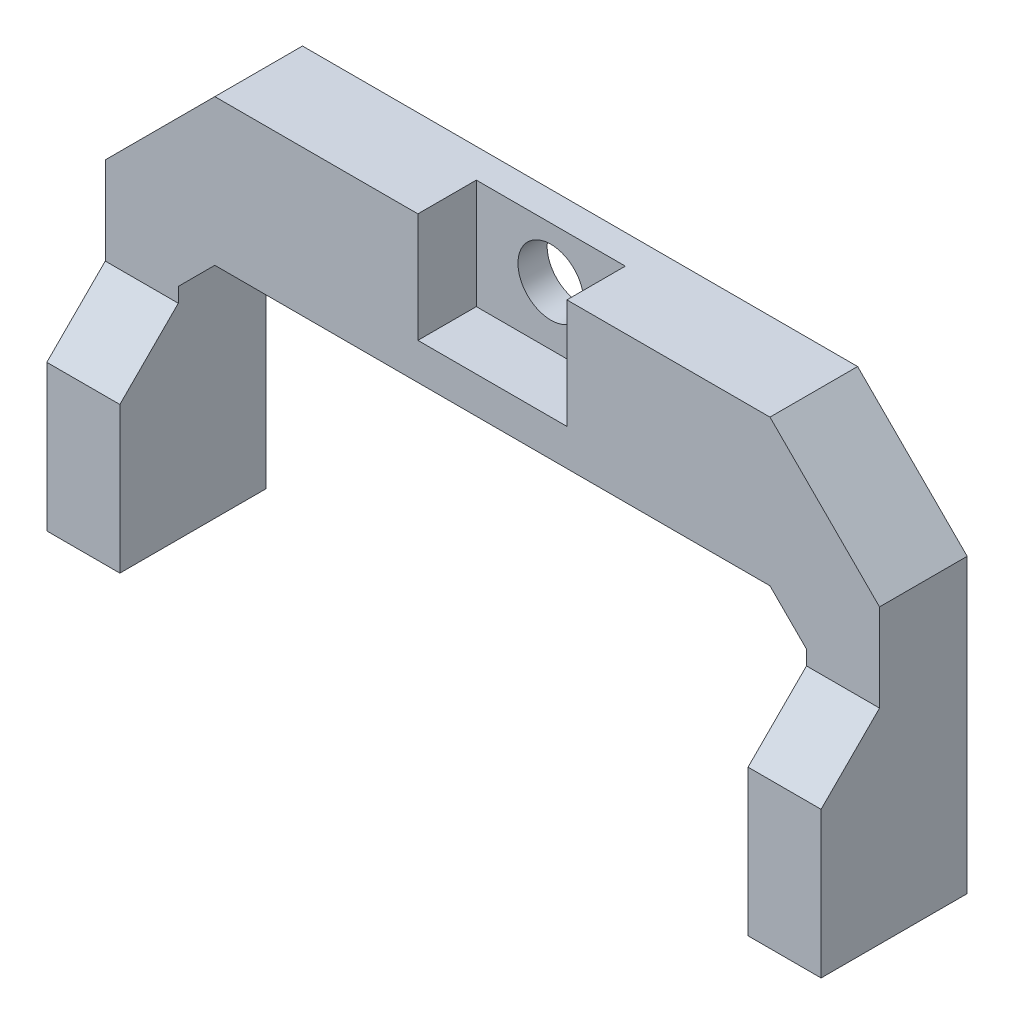
SolidWorks part; units mm, degrees
ref_plane "Front Plane" through (0, 0, 0) normal (0, 0, 1) x (1, 0, 0)
ref_plane "Top Plane" through (0, 0, 0) normal (0, 1, 0) x (1, 0, 0)
ref_plane "Right Plane" through (0, 0, 0) normal (1, 0, 0) x (0, 0, -1)
sketch "Sketch1" plane through (0, 0, 0) normal (0, 0, 1) x (1, 0, 0)
  line L0 (0, 0) -> (0, -10)
  line L1 (0, -10) -> (-19, -10)
  line L2 (-19, -10) -> (-21.5, -12.5)
  line L3 (-21.5, -12.5) -> (-21.5, -27.5)
  line L4 (-21.5, -27.5) -> (-26.5, -27.5)
  line L5 (-26.5, -27.5) -> (-26.5, -7.5)
  line L6 (-26.5, -7.5) -> (-19, 0)
  line L7 (-19, 0) -> (0, 0)
  point P0 (-14.5605, -10)
  point P9 (-38.8426, 2.4394)
  point P11 (-37.1805, -7.4866)
  point P12 (0, 14.5375)
  dimension "D1" = 135
  dimension "D2" = 21.5
  dimension "D3" = 5
  dimension "D4" = 15
  dimension "D5" = 10
  dimension "D6" = 2.5
extrude "Boss-Extrude1" add sketch "Sketch1" along normal blind 6
sketch "Sketch6" plane through (0, 0, 6) normal (0, 0, 1) x (1, 0, 0)
  line L0 (-21.5, -27.5) -> (-21.5, -12.5) construction
  line L1 (-26.5, -27.5) -> (-21.5, -27.5)
  line L2 (-26.5, -27.5) -> (-26.5, -17.5)
  line L3 (-26.5, -17.5) -> (-21.5, -17.5)
  line L4 (-21.5, -27.5) -> (-21.5, -17.5)
  dimension "D1" = 10
extrude "Boss-Extrude2" add sketch "Sketch6" along normal blind 4
sketch "Sketch3" plane through (0, 0, 6) normal (0, 0, 1) x (1, 0, 0)
  line L1 (0, 0) -> (-5.1, 0)
  line L2 (0, 0) -> (0, -7.5)
  line L3 (0, -7.5) -> (-5.1, -7.5)
  line L4 (-5.1, 0) -> (-5.1, -7.5)
  dimension "D1" = 7.5
  dimension "D2" = 5.1
extrude "Cut-Extrude1" cut sketch "Sketch3" against normal blind 4
mirror "Mirror1" about plane through (0, 0, 6) normal (-1, 0, 0) of "Boss-Extrude1", "Boss-Extrude2", "Cut-Extrude1"
hole_wizard "M4 Clearance Hole1" positions "Sketch4" profile "Sketch5" hole size "M4" standard "ANSI Metric" end condition through all
sketch "Sketch4" plane through (0, 0, 2) normal (0, 0, 1) x (1, 0, 0)
  line L0 (-5.1, -7.5) -> (5.1, -7.5) construction
  line L1 (0, -5.5) -> (0, 5.5) construction
  point P0 (0, -3.5)
  point P5 (0, -3.5)
  point P6 (-2.7424, -3.5)
  dimension "D1" = 4
sketch "Sketch5" plane through (0, -3.5, 2) normal (1, 0, 0) x (0, -1, 0)
  line L0 (0, 0) -> (0, 2)
  line L1 (0, 2) -> (2.25, 2)
  line L2 (2.25, 2) -> (2.25, 0)
  line L5 (2.25, 0) -> (0, 0)
  line L11 (0, -6.35) -> (0, 107.95) construction
  dimension "Thru Hole Dia." = 4.5
  dimension "Thru Hole Depth" = 2
chamfer "Chamfer2" distance 4 6 edges at (-26.5, -17.5, 8) (-24, -17.5, 6) (-21.5, -17.5, 8) (26.5, -17.5, 8) (21.5, -17.5, 8) (24, -17.5, 6)
equation "\"a\"=1"
